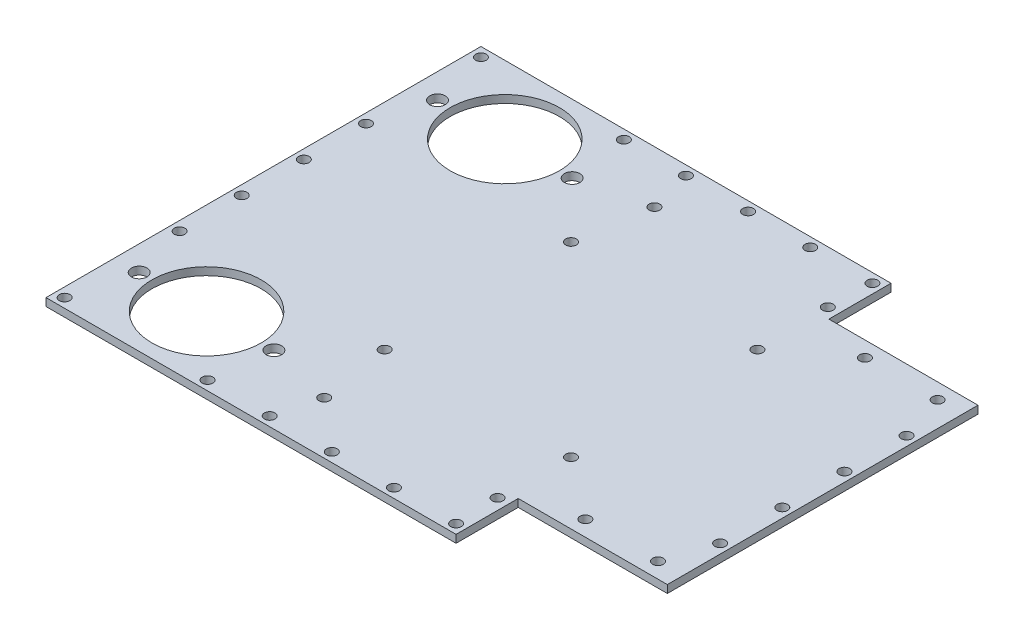
SolidWorks part; units mm, degrees
ref_plane "Front Plane" through (0, 0, 0) normal (0, 0, 1) x (1, 0, 0)
ref_plane "Top Plane" through (0, 0, 0) normal (0, 1, 0) x (1, 0, 0)
ref_plane "Right Plane" through (0, 0, 0) normal (1, 0, 0) x (0, 0, -1)
sketch "Sketch1" plane through (0, 0, 0) normal (0, 1, 0) x (1, 0, 0)
  line L1 (-217.8874, 70.6405) -> (10.7126, 70.6405)
  line L2 (-217.8874, 70.6405) -> (-217.8874, -107.1595)
  line L3 (-217.8874, -107.1595) -> (10.7126, -107.1595)
  line L4 (10.7126, 70.6405) -> (10.7126, -107.1595)
  dimension "D1" = 228.6
  dimension "D2" = 177.8
extrude "Boss-Extrude1" add sketch "Sketch1" along normal blind 3.175
sketch "Sketch2" plane through (0, 3.175, 0) normal (0, 1, 0) x (1, 0, 0)
  line L0 (-217.8874, -107.1595) -> (10.7126, -107.1595) construction
  line L1 (10.7126, -107.1595) -> (-50.2474, -107.1595)
  line L2 (10.7126, -107.1595) -> (10.7126, -81.7595)
  line L3 (10.7126, -81.7595) -> (-50.2474, -81.7595)
  line L4 (-50.2474, -107.1595) -> (-50.2474, -81.7595)
  line L5 (10.7126, -107.1595) -> (10.7126, 70.6405) construction
  line L6 (10.7126, 70.6405) -> (-217.8874, 70.6405) construction
  line L7 (10.7126, 70.6405) -> (-50.2474, 70.6405)
  line L8 (10.7126, 70.6405) -> (10.7126, 45.2405)
  line L9 (10.7126, 45.2405) -> (-50.2474, 45.2405)
  line L10 (-50.2474, 70.6405) -> (-50.2474, 45.2405)
  line L11 (-217.8874, 70.6405) -> (-217.8874, -107.1595) construction
  circle A0 centre (0.5526, 38.8905) radius 2.1717
  circle A1 centre (-29.1654, 38.8905) radius 2.1717
  circle A2 centre (0.5526, -75.4095) radius 2.1717
  circle A3 centre (-29.1654, -75.4095) radius 2.1717
  circle A4 centre (-207.7274, 42.7005) radius 3.175
  circle A5 centre (-152.6602, 42.7005) radius 3.175
  circle A6 centre (-180.1938, 42.7005) radius 22.352
  circle A7 centre (-207.7274, -79.2195) radius 3.175
  circle A8 centre (-180.1938, -79.2195) radius 22.352
  circle A9 centre (-152.6602, -79.2195) radius 3.175
  circle A10 centre (-54.6924, 49.2405) radius 2.1717
  circle A11 centre (-125.5584, 49.2405) radius 2.1717
  circle A12 centre (-125.5584, -85.7595) radius 2.1717
  circle A13 centre (-54.6924, -85.7595) radius 2.1717
  circle A14 centre (-54.0574, 66.8305) radius 2.159
  circle A15 centre (-54.0574, -103.3495) radius 2.159
  circle A16 centre (-214.0774, 66.8305) radius 2.159
  circle A17 centre (-214.0774, -103.3495) radius 2.1717
  circle A18 centre (-79.4574, 66.8305) radius 2.1717
  circle A19 centre (-104.8574, 66.8305) radius 2.1717
  circle A20 centre (-130.2574, 66.8305) radius 2.1717
  circle A21 centre (-155.6574, 66.8305) radius 2.1717
  circle A22 centre (-79.4574, -103.3495) radius 2.1717
  circle A23 centre (-104.8574, -103.3495) radius 2.1717
  circle A24 centre (-130.2574, -103.3495) radius 2.1717
  circle A25 centre (-155.6574, -103.3495) radius 2.1717
  circle A26 centre (-214.0774, 19.8405) radius 2.1717
  circle A27 centre (-214.0774, -5.5595) radius 2.1717
  circle A28 centre (-214.0774, -30.9595) radius 2.1717
  circle A29 centre (-214.0774, -56.3595) radius 2.1717
  circle A30 centre (-130.2574, 19.8405) radius 2.1717
  circle A31 centre (-130.2574, -56.3595) radius 2.1717
  circle A32 centre (6.9026, 19.8405) radius 2.1717
  circle A33 centre (6.9026, -5.5595) radius 2.1717
  circle A34 centre (6.9026, -30.9595) radius 2.1717
  circle A35 centre (6.9026, -56.3595) radius 2.1717
  circle A36 centre (-54.0574, 19.8405) radius 2.1717
  circle A37 centre (-54.0574, -56.3595) radius 2.1717
  dimension "D5" = 10.16
  dimension "D7" = 6.35
  dimension "D9" = 10.16
  dimension "D11" = 29.718
  dimension "D13" = 27.94
  dimension "D15" = 55.0672
  dimension "D17" = 10.16
  dimension "D19" = 27.5336
  dimension "D20" = 55.0672
  dimension "D21" = 21.4
  dimension "D22" = 70.866
  dimension "D24" = 135
  dimension "D25" = 3.81
  dimension "D27" = 3.81
  dimension "D30" = 3.81
  dimension "D32" = 3.81
  dimension "D34" = 25.4
  dimension "D35" = 25.4
  dimension "D38" = 25.4
  dimension "D40" = 25.4
  dimension "D42" = 3.81
  dimension "D44" = 25.4
  dimension "D46" = 25.4
  dimension "D48" = 25.4
  dimension "D50" = 46.99
  dimension "D52" = 25.4
  dimension "D53" = 25.4
  dimension "D54" = 25.4
  dimension "D55" = 46.99
  dimension "D57" = 46.99
  dimension "D59" = 3.81
  dimension "D60" = 25.4
  dimension "D61" = 25.4
  dimension "D62" = 25.4
  dimension "D66" = 46.99
  dimension "D68" = 60.96
  dimension "D1" = 25.4
  dimension "D2" = 60.96
  dimension "D3" = 60.96
  dimension "D4" = 25.4
  dimension "D6" = 6.35
  dimension "D8" = 29.718
  dimension "D10" = 6.35
  dimension "D12" = 6.35
  dimension "D14" = 10.16
  dimension "D16" = 27.5336
  dimension "D18" = 27.94
  dimension "D23" = 4.445
  dimension "D26" = 3.81
  dimension "D28" = 3.81
  dimension "D29" = 70.866
  dimension "D31" = 3.81
  dimension "D33" = 3.81
  dimension "D36" = 3.81
  dimension "D37" = 3.81
  dimension "D39" = 3.81
  dimension "D41" = 3.81
  dimension "D43" = 25.4
  dimension "D45" = 3.81
  dimension "D47" = 3.81
  dimension "D49" = 3.81
  dimension "D51" = 3.81
  dimension "D56" = 83.82
  dimension "D58" = 83.82
  dimension "D63" = 3.81
  dimension "D64" = 3.81
  dimension "D65" = 3.81
  dimension "D67" = 60.96
  dimension "D69" = 46.99
extrude "Cut-Extrude1" cut sketch "Sketch2" against normal blind 3.175
